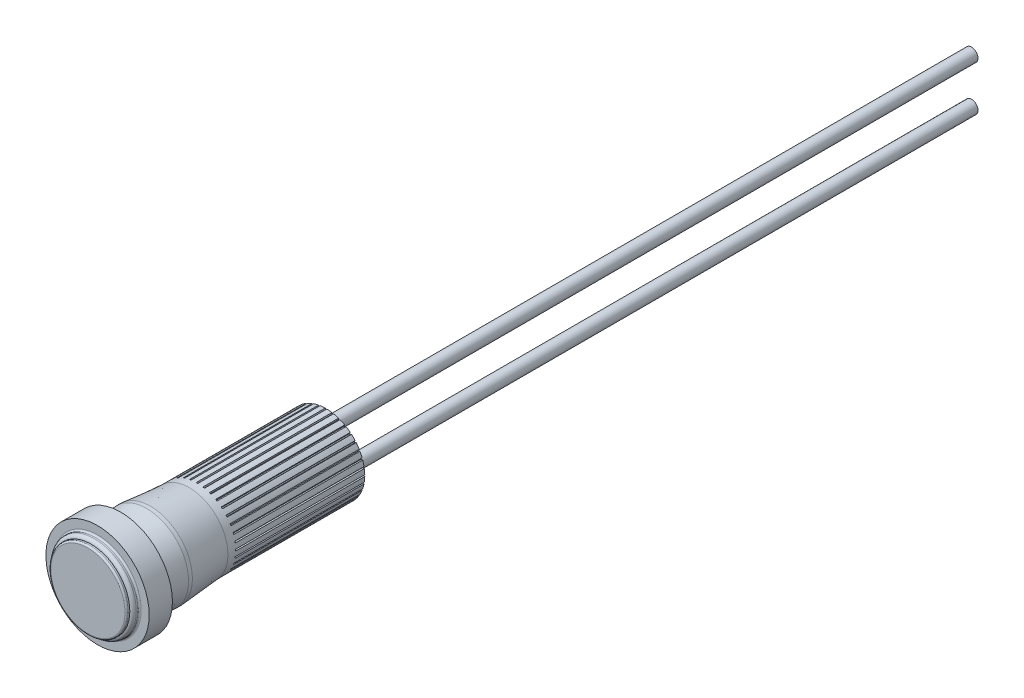
SolidWorks part; units mm, degrees
material "Chrome Stainless Steel"
ref_plane "Front Plane" through (0, 0, 0) normal (0, 0, 1) x (1, 0, 0)
ref_plane "Top Plane" through (0, 0, 0) normal (0, 1, 0) x (1, 0, 0)
ref_plane "Right Plane" through (0, 0, 0) normal (1, 0, 0) x (0, 0, -1)
sketch "Sketch1" plane through (0, 0, 0) normal (0, 0, 1) x (1, 0, 0)
  circle A0 centre (0, 0) radius 8
  dimension "D1" = 16
extrude "Boss-Extrude1" add sketch "Sketch1" along normal blind 5.1
sketch "Sketch2" plane through (0, 0, 5.1) normal (0, 0, 1) x (1, 0, 0)
  circle A0 centre (0, 0) radius 6.5
  circle A1 centre (0, 0) radius 8
  dimension "D1" = 13
extrude "Cut-Extrude1" cut sketch "Sketch2" against normal blind 1.5
sketch "Sketch3" plane through (0, 0, 5.1) normal (0, 0, 1) x (1, 0, 0)
  circle A0 centre (0, 0) radius 7
  circle A1 centre (0, 0) radius 6
  dimension "D1" = 12
extrude "Cut-Extrude2" cut sketch "Sketch3" against normal blind 0.5
fillet "Fillet1" radius 0.5 1 edges at (6.5, 0, 4.6)
fillet "Fillet2" radius 0.25 1 edges at (6, 0, 5.1)
fillet "Fillet3" radius 0.25 1 edges at (6.5, 0, 3.6)
sketch "Sketch4" plane through (0, 0, 0) normal (1, 0, 0) x (0, 0, -1)
  line L0 (0, 0) -> (39.4844, 0) construction
  line L1 (0, 6) -> (4, 6.5)
  line L2 (0, -8) -> (0, 8) construction
  line L3 (4, 6.5) -> (4.6, 6.5)
  line L4 (4.6, 6.5) -> (10.6, 6)
  line L5 (10.6, 6) -> (31.8, 6)
  line L6 (31.8, 6) -> (31.8, 0)
  line L7 (0, 6) -> (0, 0)
  line L8 (0, 0) -> (31.8, 0)
  line L9 (0, 6) -> (10.6, 6) construction
  dimension "D1" = 0.5
  dimension "D2" = 31.8
  dimension "D3" = 10.6
  dimension "D4" = 4
  dimension "D5" = 6
  dimension "D6" = 6
revolve "Revolve1" add sketch "Sketch4" angle 360 about L0
sketch "Sketch5" plane through (0, 0, -31.8) normal (0, 0, -1) x (-1, 0, 0)
  line L0 (0, 0) -> (0, 8.4459) construction
  line L1 (0.125, 5.75) -> (0.125, 6.25) construction
  line L2 (0.9188, 5.9306) -> (1.165, 5.8871)
  line L3 (0.125, 6.25) -> (-0.125, 6.25)
  line L4 (-0.125, 5.75) -> (-0.125, 6.25) construction
  line L5 (0.125, 5.75) -> (-0.125, 6.25) construction
  line L6 (0.125, 6.25) -> (-0.125, 5.75) construction
  line L7 (-0.125, 6) -> (-0.075, 5.75)
  line L8 (0.125, 6) -> (0.075, 5.75)
  line L9 (-0.075, 5.75) -> (0.075, 5.75)
  line L10 (0.9188, 5.9306) -> (0.9246, 5.6757)
  line L11 (0.9246, 5.6757) -> (1.0723, 5.6496)
  line L12 (1.165, 5.8871) -> (1.0723, 5.6496)
  line L13 (1.9347, 5.6809) -> (2.1696, 5.5954)
  line L14 (1.9347, 5.6809) -> (1.8961, 5.4289)
  line L15 (1.8961, 5.4289) -> (2.0371, 5.3776)
  line L16 (2.1696, 5.5954) -> (2.0371, 5.3776)
  line L17 (2.8917, 5.2587) -> (3.1083, 5.1337)
  line L18 (2.8917, 5.2587) -> (2.81, 5.0171)
  line L19 (-0.125, 6) -> (0.125, 6)
  line L20 (2.81, 5.0171) -> (2.94, 4.9421)
  line L21 (3.1083, 5.1337) -> (2.94, 4.9421)
  line L22 (3.761, 4.6766) -> (3.9525, 4.5159)
  line L23 (3.761, 4.6766) -> (3.6386, 4.453)
  line L24 (3.6386, 4.453) -> (3.7535, 4.3565)
  line L25 (3.9525, 4.5159) -> (3.7535, 4.3565)
  line L26 (4.5159, 3.9525) -> (4.6766, 3.761)
  line L27 (4.5159, 3.9525) -> (4.3565, 3.7535)
  line L28 (4.3565, 3.7535) -> (4.453, 3.6386)
  line L29 (4.6766, 3.761) -> (4.453, 3.6386)
  line L30 (5.1337, 3.1083) -> (5.2587, 2.8917)
  line L31 (5.1337, 3.1083) -> (4.9421, 2.94)
  line L32 (4.9421, 2.94) -> (5.0171, 2.81)
  line L33 (5.2587, 2.8917) -> (5.0171, 2.81)
  line L34 (5.5954, 2.1696) -> (5.6809, 1.9347)
  line L35 (5.5954, 2.1696) -> (5.3776, 2.0371)
  line L36 (5.3776, 2.0371) -> (5.4289, 1.8961)
  line L37 (5.6809, 1.9347) -> (5.4289, 1.8961)
  line L38 (5.8871, 1.165) -> (5.9306, 0.9188)
  line L39 (5.8871, 1.165) -> (5.6496, 1.0723)
  line L40 (5.6496, 1.0723) -> (5.6757, 0.9246)
  line L41 (5.9306, 0.9188) -> (5.6757, 0.9246)
  line L42 (6, 0.125) -> (6, -0.125)
  line L43 (6, 0.125) -> (5.75, 0.075)
  line L44 (5.75, 0.075) -> (5.75, -0.075)
  line L45 (6, -0.125) -> (5.75, -0.075)
  line L46 (5.9306, -0.9188) -> (5.8871, -1.165)
  line L47 (5.9306, -0.9188) -> (5.6757, -0.9246)
  line L48 (5.6757, -0.9246) -> (5.6496, -1.0723)
  line L49 (5.8871, -1.165) -> (5.6496, -1.0723)
  line L50 (5.6809, -1.9347) -> (5.5954, -2.1696)
  line L51 (5.6809, -1.9347) -> (5.4289, -1.8961)
  line L52 (5.4289, -1.8961) -> (5.3776, -2.0371)
  line L53 (5.5954, -2.1696) -> (5.3776, -2.0371)
  line L54 (5.2587, -2.8917) -> (5.1337, -3.1083)
  line L55 (5.2587, -2.8917) -> (5.0171, -2.81)
  line L56 (5.0171, -2.81) -> (4.9421, -2.94)
  line L57 (5.1337, -3.1083) -> (4.9421, -2.94)
  line L58 (4.6766, -3.761) -> (4.5159, -3.9525)
  line L59 (4.6766, -3.761) -> (4.453, -3.6386)
  line L60 (4.453, -3.6386) -> (4.3565, -3.7535)
  line L61 (4.5159, -3.9525) -> (4.3565, -3.7535)
  line L62 (3.9525, -4.5159) -> (3.761, -4.6766)
  line L63 (3.9525, -4.5159) -> (3.7535, -4.3565)
  line L64 (3.7535, -4.3565) -> (3.6386, -4.453)
  line L65 (3.761, -4.6766) -> (3.6386, -4.453)
  line L66 (3.1083, -5.1337) -> (2.8917, -5.2587)
  line L67 (3.1083, -5.1337) -> (2.94, -4.9421)
  line L68 (2.94, -4.9421) -> (2.81, -5.0171)
  line L69 (2.8917, -5.2587) -> (2.81, -5.0171)
  line L70 (2.1696, -5.5954) -> (1.9347, -5.6809)
  line L71 (2.1696, -5.5954) -> (2.0371, -5.3776)
  line L72 (2.0371, -5.3776) -> (1.8961, -5.4289)
  line L73 (1.9347, -5.6809) -> (1.8961, -5.4289)
  line L74 (1.165, -5.8871) -> (0.9188, -5.9306)
  line L75 (1.165, -5.8871) -> (1.0723, -5.6496)
  line L76 (1.0723, -5.6496) -> (0.9246, -5.6757)
  line L77 (0.9188, -5.9306) -> (0.9246, -5.6757)
  line L78 (0.125, -6) -> (-0.125, -6)
  line L79 (0.125, -6) -> (0.075, -5.75)
  line L80 (0.075, -5.75) -> (-0.075, -5.75)
  line L81 (-0.125, -6) -> (-0.075, -5.75)
  line L82 (-0.9188, -5.9306) -> (-1.165, -5.8871)
  line L83 (-0.9188, -5.9306) -> (-0.9246, -5.6757)
  line L84 (-0.9246, -5.6757) -> (-1.0723, -5.6496)
  line L85 (-1.165, -5.8871) -> (-1.0723, -5.6496)
  line L86 (-1.9347, -5.6809) -> (-2.1696, -5.5954)
  line L87 (-1.9347, -5.6809) -> (-1.8961, -5.4289)
  line L88 (-1.8961, -5.4289) -> (-2.0371, -5.3776)
  line L89 (-2.1696, -5.5954) -> (-2.0371, -5.3776)
  line L90 (-2.8917, -5.2587) -> (-3.1083, -5.1337)
  line L91 (-2.8917, -5.2587) -> (-2.81, -5.0171)
  line L92 (-2.81, -5.0171) -> (-2.94, -4.9421)
  line L93 (-3.1083, -5.1337) -> (-2.94, -4.9421)
  line L94 (-3.761, -4.6766) -> (-3.9525, -4.5159)
  line L95 (-3.761, -4.6766) -> (-3.6386, -4.453)
  line L96 (-3.6386, -4.453) -> (-3.7535, -4.3565)
  line L97 (-3.9525, -4.5159) -> (-3.7535, -4.3565)
  line L98 (-4.5159, -3.9525) -> (-4.6766, -3.761)
  line L99 (-4.5159, -3.9525) -> (-4.3565, -3.7535)
  line L100 (-4.3565, -3.7535) -> (-4.453, -3.6386)
  line L101 (-4.6766, -3.761) -> (-4.453, -3.6386)
  line L102 (-5.1337, -3.1083) -> (-5.2587, -2.8917)
  line L103 (-5.1337, -3.1083) -> (-4.9421, -2.94)
  line L104 (-4.9421, -2.94) -> (-5.0171, -2.81)
  line L105 (-5.2587, -2.8917) -> (-5.0171, -2.81)
  line L106 (-5.5954, -2.1696) -> (-5.6809, -1.9347)
  line L107 (-5.5954, -2.1696) -> (-5.3776, -2.0371)
  line L108 (-5.3776, -2.0371) -> (-5.4289, -1.8961)
  line L109 (-5.6809, -1.9347) -> (-5.4289, -1.8961)
  line L110 (-5.8871, -1.165) -> (-5.9306, -0.9188)
  line L111 (-5.8871, -1.165) -> (-5.6496, -1.0723)
  line L112 (-5.6496, -1.0723) -> (-5.6757, -0.9246)
  line L113 (-5.9306, -0.9188) -> (-5.6757, -0.9246)
  line L114 (-6, -0.125) -> (-6, 0.125)
  line L115 (-6, -0.125) -> (-5.75, -0.075)
  line L116 (-5.75, -0.075) -> (-5.75, 0.075)
  line L117 (-6, 0.125) -> (-5.75, 0.075)
  line L118 (-5.9306, 0.9188) -> (-5.8871, 1.165)
  line L119 (-5.9306, 0.9188) -> (-5.6757, 0.9246)
  line L120 (-5.6757, 0.9246) -> (-5.6496, 1.0723)
  line L121 (-5.8871, 1.165) -> (-5.6496, 1.0723)
  line L122 (-5.6809, 1.9347) -> (-5.5954, 2.1696)
  line L123 (-5.6809, 1.9347) -> (-5.4289, 1.8961)
  line L124 (-5.4289, 1.8961) -> (-5.3776, 2.0371)
  line L125 (-5.5954, 2.1696) -> (-5.3776, 2.0371)
  line L126 (-5.2587, 2.8917) -> (-5.1337, 3.1083)
  line L127 (-5.2587, 2.8917) -> (-5.0171, 2.81)
  line L128 (-5.0171, 2.81) -> (-4.9421, 2.94)
  line L129 (-5.1337, 3.1083) -> (-4.9421, 2.94)
  line L130 (-4.6766, 3.761) -> (-4.5159, 3.9525)
  line L131 (-4.6766, 3.761) -> (-4.453, 3.6386)
  line L132 (-4.453, 3.6386) -> (-4.3565, 3.7535)
  line L133 (-4.5159, 3.9525) -> (-4.3565, 3.7535)
  line L134 (-3.9525, 4.5159) -> (-3.761, 4.6766)
  line L135 (-3.9525, 4.5159) -> (-3.7535, 4.3565)
  line L136 (-3.7535, 4.3565) -> (-3.6386, 4.453)
  line L137 (-3.761, 4.6766) -> (-3.6386, 4.453)
  line L138 (-3.1083, 5.1337) -> (-2.8917, 5.2587)
  line L139 (-3.1083, 5.1337) -> (-2.94, 4.9421)
  line L140 (-2.94, 4.9421) -> (-2.81, 5.0171)
  line L141 (-2.8917, 5.2587) -> (-2.81, 5.0171)
  line L142 (-2.1696, 5.5954) -> (-1.9347, 5.6809)
  line L143 (-2.1696, 5.5954) -> (-2.0371, 5.3776)
  line L144 (-2.0371, 5.3776) -> (-1.8961, 5.4289)
  line L145 (-1.9347, 5.6809) -> (-1.8961, 5.4289)
  line L146 (-1.165, 5.8871) -> (-0.9188, 5.9306)
  line L147 (-1.165, 5.8871) -> (-1.0723, 5.6496)
  line L148 (-1.0723, 5.6496) -> (-0.9246, 5.6757)
  line L149 (-0.9188, 5.9306) -> (-0.9246, 5.6757)
  circle A0 centre (0, 0) radius 6 construction
  point P4 (0, 6)
  point P35 (0, 0)
  point P158 (0, 0)
  dimension "D1" = 0.5
  dimension "D2" = 0.25
  dimension "D3" = 0.15
  dimension "D4" = 0.05
extrude "Cut-Extrude3" cut sketch "Sketch5" against normal blind 20 contours L137 L0 L135 L136 | L141 L0 L139 L140 | L145 L0 L143 L144 | L149 L0 L147 L148 | L130 L133 L132 L131 | L8 L9 L7 L19 | L2 L12 L11 L10 | L13 L16 L15 L14 | L17 L21 L20 L18 | L22 L25 L24 L23 | L26 L29 L28 L27 | L33 L32 L31 L30 | L34 L37 L36 L35 | L41 L40 L39 L38 | L45 L44 L43 L42 | L49 L48 L47 L46 | L50 L53 L52 L51 | L55 L56 L57 L54 | L59 L60 L61 L58 | L65 L64 L63 L62 | L66 L69 L68 L67 | L71 L72 L73 L70 | L75 L76 L77 L74 | L79 L80 L81 L78 | L85 L84 L83 L82 | L86 L89 L88 L87 | L90 L93 L92 L91 | L95 L96 L97 L94 | L101 L100 L99 L98 | L102 L105 L104 L103 | L106 L109 L108 L107 | L110 L113 L112 L111 | L114 L117 L116 L115 | L118 L121 L120 L119 | L126 L129 L128 L127 | L122 L125 L124 L123 region at (3.7831, 4.5085, -31.8) region at (2.9427, 5.0969, -31.8) region at (2.0129, 5.5305, -31.8) region at (1.022, 5.796, -31.8)
sketch "Sketch6" plane through (0, 0, -31.8) normal (0, 0, -1) x (-1, 0, 0)
  line L0 (-10.2302, 0) -> (12.9337, 0) construction
  circle A0 centre (0, 3.5) radius 1
  circle A1 centre (0, -3.5) radius 1
  dimension "D1" = 2
  dimension "D2" = 3.5
extrude "Boss-Extrude2" add sketch "Sketch6" along normal blind 100
equation "\"1.5.00mm\"=2"
